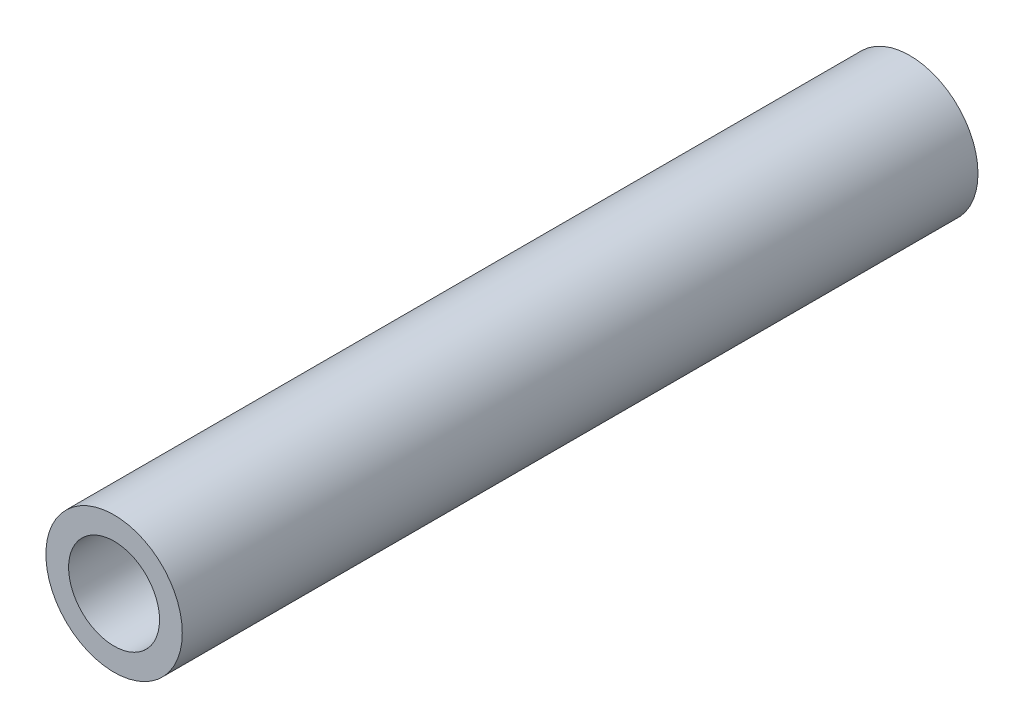
SolidWorks part; units mm, degrees
material "C-Fibra di vetro"
ref_plane "Piano frontale" through (0, 0, 0) normal (0, 0, 1) x (1, 0, 0)
ref_plane "Piano superiore" through (0, 0, 0) normal (0, 1, 0) x (1, 0, 0)
ref_plane "Piano destro" through (0, 0, 0) normal (1, 0, 0) x (0, 0, -1)
sketch "Schizzo1" plane through (0, 0, 0) normal (0, 0, 1) x (1, 0, 0)
  circle A0 centre (207, -26.4239) radius 3
  circle A1 centre (207, -26.4239) radius 2
  dimension "D1" = 1
  dimension "D2" = 6
extrude "Estrusione-Estrusione1" add sketch "Schizzo1" along normal up to surface (35 mm away)
